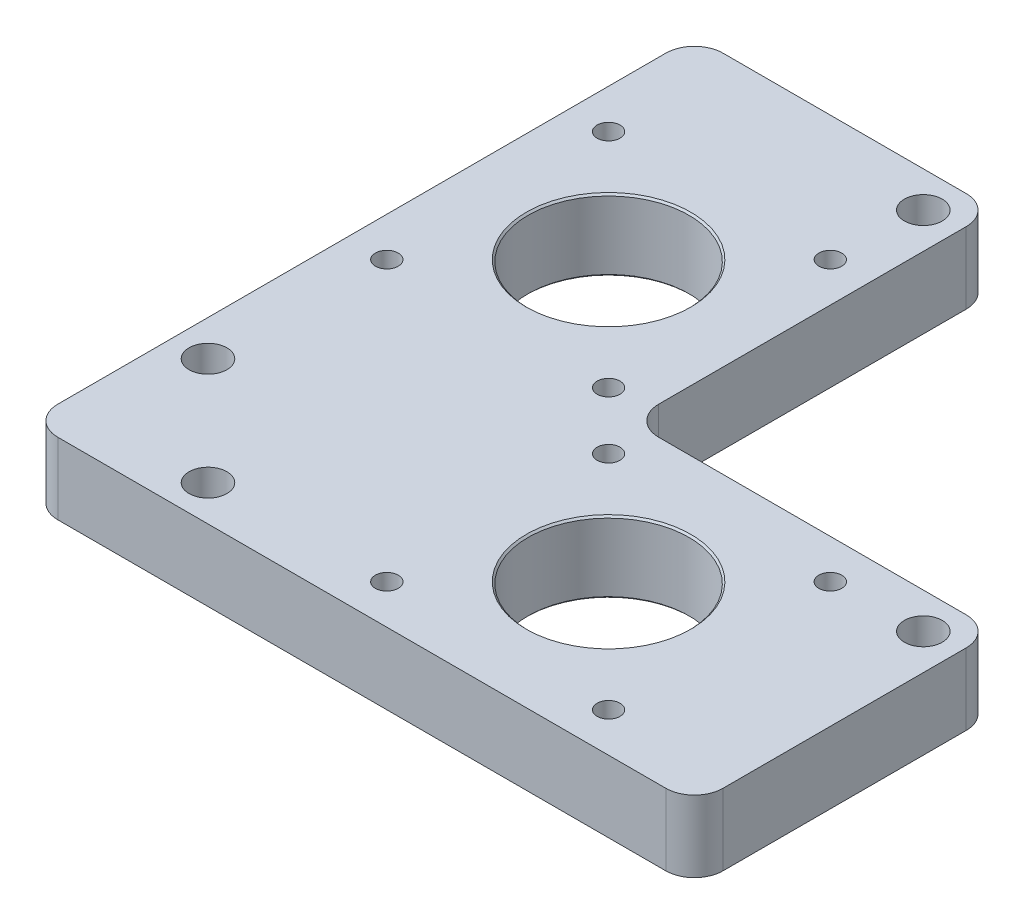
SolidWorks part; units mm, degrees
material "AISI 1045 Steel, cold drawn"
ref_plane "Front Plane" through (0, 0, 0) normal (0, 0, 1) x (1, 0, 0)
ref_plane "Top Plane" through (0, 0, 0) normal (0, 1, 0) x (1, 0, 0)
ref_plane "Right Plane" through (0, 0, 0) normal (1, 0, 0) x (0, 0, -1)
sketch "Sketch1" plane through (0, 0, 0) normal (0, 1, 0) x (1, 0, 0)
  line L1 (60, -21) -> (18, -21) construction
  line L2 (60, -21) -> (60, 21) construction
  line L3 (60, 21) -> (18, 21) construction
  line L4 (18, -21) -> (18, 21) construction
  line L5 (60, -21) -> (18, 21) construction
  line L6 (60, 21) -> (18, -21) construction
  line L7 (21, 18) -> (-21, 18) construction
  line L8 (21, 18) -> (21, 60) construction
  line L9 (21, 60) -> (-21, 60) construction
  line L10 (-21, 18) -> (-21, 60) construction
  line L11 (21, 18) -> (-21, 60) construction
  line L12 (21, 60) -> (-21, 18) construction
  line L14 (60, -21) -> (60, 21)
  line L15 (60, 21) -> (21, 21)
  line L16 (21, 21) -> (21, 60)
  line L17 (21, 60) -> (-21, 60)
  line L18 (-21, 60) -> (-21, 18)
  line L19 (-21, 18) -> (18, 18)
  line L20 (18, 18) -> (18, -21)
  line L21 (18, -21) -> (60, -21)
  point P0 (39, 0)
  point P5 (0, 39)
  dimension "D1" = 42
  dimension "D2" = 39
  dimension "D3" = 39
extrude "Boss-Extrude1" add sketch "Sketch1" along normal blind 10
hole_wizard "Ø22.5 (22.5) Diameter Hole1" positions "Sketch5" profile "Sketch7" hole size "Ø22.5" standard "ANSI Metric" end condition through all
sketch "Sketch5" plane through (0, 10, 0) normal (0, 1, 0) x (1, 0, 0)
  point P0 (0, 39)
  point P3 (39, 0)
sketch "Sketch7" plane through (0, 10, -39) normal (1, 0, 0) x (0, 0, 1)
  line L0 (0, 0) -> (0, 10)
  line L1 (0, 10) -> (11.25, 10)
  line L2 (11.25, 10) -> (11.25, 0)
  line L5 (11.25, 0) -> (0, 0)
  line L11 (0, -6.35) -> (0, 107.95) construction
  dimension "Thru Hole Dia." = 22.5
  dimension "Thru Hole Depth" = 10
sketch "Sketch8" plane through (0, 0, 0) normal (0, 1, 0) x (1, 0, 0)
  line L0 (21, 60) -> (-21, 18) construction
  line L1 (15.5, 23.5) -> (-15.5, 23.5)
  line L2 (15.5, 23.5) -> (15.5, 54.5)
  line L3 (15.5, 54.5) -> (-15.5, 54.5)
  line L4 (-15.5, 23.5) -> (-15.5, 54.5)
  line L5 (15.5, 23.5) -> (-15.5, 54.5) construction
  line L6 (15.5, 54.5) -> (-15.5, 23.5) construction
  line L7 (21, 18) -> (-21, 60) construction
  line L8 (60, 21) -> (18, -21) construction
  line L9 (23.5, -15.5) -> (54.5, -15.5)
  line L10 (23.5, -15.5) -> (23.5, 15.5)
  line L11 (23.5, 15.5) -> (54.5, 15.5)
  line L12 (54.5, -15.5) -> (54.5, 15.5)
  line L13 (23.5, -15.5) -> (54.5, 15.5) construction
  line L14 (23.5, 15.5) -> (54.5, -15.5) construction
  point P0 (0, 39)
  point P9 (39, 0)
  dimension "D1" = 31
hole_wizard "CBORE for M3 SHCS1" positions "Sketch9" profile "Sketch10" counterbore size "M3" standard "ANSI Metric" end condition through all
sketch "Sketch9" plane through (0, 0, 0) normal (0, -1, 0) x (-1, 0, 0)
  point P0 (-54.5, 15.5)
  point P3 (-23.5, 15.5)
  point P6 (-23.5, -15.5)
  point P9 (-54.5, -15.5)
  point P12 (-15.5, 54.5)
  point P15 (-15.5, 23.5)
  point P18 (15.5, 23.5)
  point P21 (15.5, 54.5)
sketch "Sketch10" plane through (54.5, 0, -15.5) normal (1, 0, 0) x (0, 0, -1)
  line L0 (0, 0) -> (0, 10)
  line L1 (0, 10) -> (1.6, 10)
  line L3 (1.6, 10) -> (1.6, 3)
  line L4 (1.6, 3) -> (3.25, 3)
  line L5 (3.25, 3) -> (3.25, 0)
  line L7 (3.25, 0) -> (0, 0)
  line L11 (0, -6.35) -> (0, 107.95) construction
  dimension "Thru Hole Dia." = 3.2
  dimension "Thru Hole Depth" = 10
  dimension "C'Bore Dia." = 6.5
  dimension "C'Bore Depth" = 3
sketch "Sketch16" plane through (0, 10, 0) normal (0, 1, 0) x (1, 0, 0)
  line L1 (17.1, 17.1) -> (-21, 17.1)
  line L2 (17.1, 17.1) -> (17.1, -21)
  line L6 (-21, 17.1) -> (-21, 18)
  line L7 (-21, 18) -> (18, 18)
  line L8 (18, 18) -> (18, -21)
  line L9 (18, -21) -> (17.1, -21)
  circle A0 centre (39, 0) radius 11.25 construction
  dimension "D1" = 21.9
extrude "Boss-Extrude2" add sketch "Sketch16" against normal up to surface (10 mm away) up to face at (54.5, 0, -18.75)
ref_plane "Plane1" through (0, 0, 0) normal (0.7071, 0, 0.7071) x (0.7071, 0, -0.7071)
sketch "Sketch17" plane through (0, 10, 0) normal (0, 1, 0) x (1, 0, 0)
  line L0 (17.1, -21) -> (60, -21) construction
  line L1 (60, 21) -> (72, 21)
  line L2 (60, 21) -> (60, -21)
  line L3 (60, -21) -> (72, -21)
  line L4 (72, 21) -> (72, -21)
  line L5 (60, -21) -> (60, 21) construction
  dimension "D1" = 12
extrude "Boss-Extrude3" add sketch "Sketch17" against normal up to surface (10 mm away) up to face at (54.5, 0, -18.75)
hole_wizard "M5 Clearance Hole1" positions "Sketch18" profile "Sketch19" hole size "M5" standard "ANSI Metric" end condition through all
sketch "Sketch18" plane through (0, 10, 0) normal (0, 1, 0) x (1, 0, 0)
  line L0 (72, 21) -> (21, 21) construction
  line L1 (72, -21) -> (72, 21) construction
  point P0 (67, 16)
  dimension "D1" = 5
  dimension "D2" = 5
sketch "Sketch19" plane through (67, 10, -16) normal (1, 0, 0) x (0, 0, 1)
  line L0 (0, 0) -> (0, 10)
  line L1 (0, 10) -> (2.65, 10)
  line L2 (2.65, 10) -> (2.65, 0)
  line L5 (2.65, 0) -> (0, 0)
  line L11 (0, -6.35) -> (0, 107.95) construction
  dimension "Thru Hole Dia." = 5.3
  dimension "Thru Hole Depth" = 10
mirror "Mirror1" about plane through (0, 0, 0) normal (0.7071, 0, 0.7071) of "Boss-Extrude3", "M5 Clearance Hole1"
sketch "Sketch20" plane through (0, 10, 0) normal (0, 1, 0) x (1, 0, 0)
  line L0 (-21, 72) -> (-21, 17.1) construction
  line L1 (-21, 17.1) -> (17.1, 17.1)
  line L2 (-21, 17.1) -> (-21, -21)
  line L3 (-21, -21) -> (17.1, -21)
  line L4 (17.1, 17.1) -> (17.1, -21)
  line L5 (-21, 17.1) -> (17.1, 17.1) construction
  point P7 (-21, 17.1)
extrude "Boss-Extrude4" add sketch "Sketch20" against normal up to surface (10 mm away) up to face at (16, 0, -64.35)
hole_wizard "M5 Clearance Hole2" positions "Sketch21" profile "Sketch23" hole size "M5" standard "ANSI Metric" end condition through all
sketch "Sketch21" plane through (0, 10, 0) normal (0, 1, 0) x (1, 0, 0)
  line L0 (-21, -21) -> (72, -21) construction
  line L1 (-16, -1) -> (-1, -1) construction
  line L2 (-1, -1) -> (-1, -16) construction
  line L4 (-21, 72) -> (-21, -21) construction
  point P0 (-16, -1)
  point P2 (-1, -16)
  dimension "D1" = 5
  dimension "D2" = 20
  dimension "D3" = 20
sketch "Sketch23" plane through (-16, 10, 1) normal (1, 0, 0) x (0, 0, 1)
  line L0 (0, 0) -> (0, 10)
  line L1 (0, 10) -> (2.65, 10)
  line L2 (2.65, 10) -> (2.65, 0)
  line L5 (2.65, 0) -> (0, 0)
  line L11 (0, -6.35) -> (0, 107.95) construction
  dimension "Thru Hole Dia." = 5.3
  dimension "Thru Hole Depth" = 10
fillet "Fillet6" radius 4 6 edges at (72, 5, 21) (72, 5, -21) (21, 5, -21) (21, 5, -72) (-21, 5, -72) (-21, 5, 21)
chamfer "Chamfer1" distance 0.25 angle 45 4 edges at (39, 10, 11.25) (39, 0, 11.25) (0, 10, -27.75) (0, 0, -27.75)
